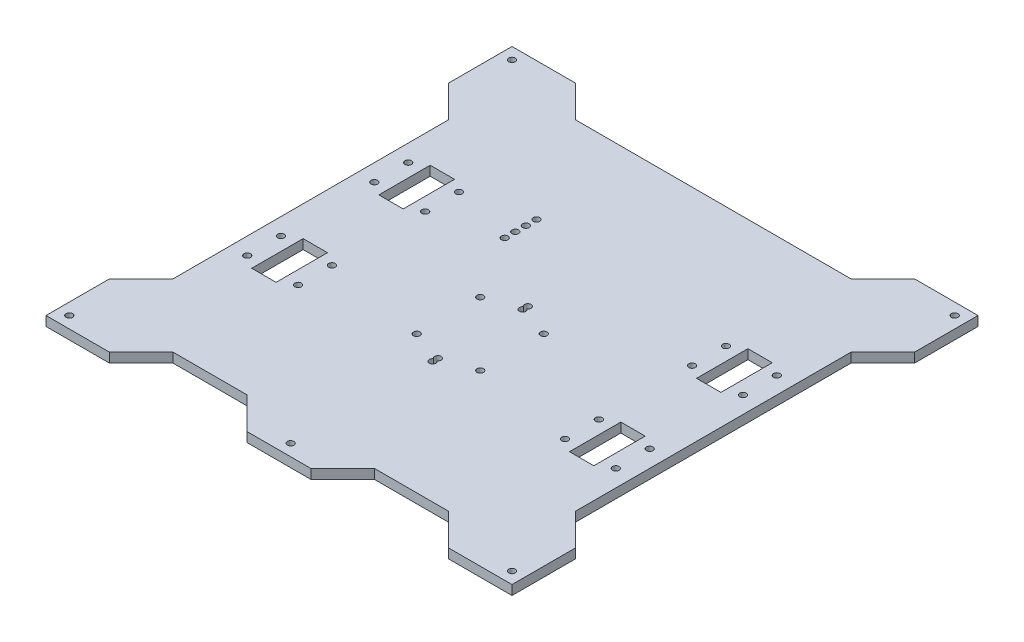
SolidWorks part; units mm, degrees
ref_plane "Front Plane" through (0, 0, 0) normal (0, 0, 1) x (1, 0, 0)
ref_plane "Top Plane" through (0, 0, 0) normal (0, 1, 0) x (1, 0, 0)
ref_plane "Right Plane" through (0, 0, 0) normal (1, 0, 0) x (0, 0, -1)
sketch "Sketch1" plane through (0, 0, 0) normal (0, 1, 0) x (1, 0, 0)
  line L1 (-110, 110) -> (110, 110)
  line L2 (-110, 110) -> (-110, -110)
  line L3 (-110, -110) -> (110, -110)
  line L4 (110, 110) -> (110, -110)
  line L5 (-110, 110) -> (110, -110) construction
  line L6 (-110, -110) -> (110, 110) construction
  point P0 (0, 0)
  dimension "D1" = 220
  dimension "D2" = 220
extrude "Square" add sketch "Sketch1" along normal blind 4.5
sketch "Sketch2" plane through (0, 4.5, 0) normal (0, 1, 0) x (1, 0, 0)
  line L0 (0, 110) -> (0, -110) construction
  line L1 (110, 110) -> (-110, 110) construction
  line L2 (-110, -110) -> (110, -110) construction
  line L3 (-110, 0) -> (110, 0) construction
  line L4 (-110, 110) -> (-110, -110) construction
  line L5 (110, -110) -> (110, 110) construction
  line L6 (75, 110) -> (75, -110) construction
  line L7 (75, 30) -> (0, 30) construction
  line L8 (75, -30) -> (0, -30) construction
  circle A0 centre (87, 38) radius 1.55
  circle A1 centre (87, 22) radius 1.55
  circle A2 centre (63, 22) radius 1.55
  circle A3 centre (63, 38) radius 1.55
  circle A4 centre (-63, 38) radius 1.55
  circle A5 centre (-63, 22) radius 1.55
  circle A6 centre (-87, 22) radius 1.55
  circle A7 centre (-87, 38) radius 1.55
  circle A8 centre (-87, 22) radius 1.55
  circle A9 centre (-87, 38) radius 1.55
  circle A10 centre (-63, 38) radius 1.55
  circle A11 centre (-63, 22) radius 1.55
  circle A12 centre (63, 22) radius 1.55
  circle A13 centre (63, 38) radius 1.55
  circle A14 centre (87, 38) radius 1.55
  circle A15 centre (87, 22) radius 1.55
  circle A16 centre (87, -22) radius 1.55
  circle A17 centre (87, -38) radius 1.55
  circle A18 centre (63, -38) radius 1.55
  circle A19 centre (63, -22) radius 1.55
  circle A20 centre (-63, -22) radius 1.55
  circle A21 centre (-63, -38) radius 1.55
  circle A22 centre (-87, -38) radius 1.55
  circle A23 centre (-87, -22) radius 1.55
  circle A24 centre (-87, -38) radius 1.55
  circle A25 centre (-87, -22) radius 1.55
  circle A26 centre (-63, -22) radius 1.55
  circle A27 centre (-63, -38) radius 1.55
  circle A28 centre (63, -38) radius 1.55
  circle A29 centre (63, -22) radius 1.55
  circle A30 centre (87, -22) radius 1.55
  circle A31 centre (87, -38) radius 1.55
  dimension "D6" = 3.1
  dimension "D7" = 3.1
  dimension "D1" = 75
  dimension "D2" = 30
  dimension "D3" = 16
  dimension "D5" = 12
extrude "LM8UU-Holders" cut sketch "Sketch2" against normal through all contours A7 | A6 | A5 | A4 | A20 | A21 | A22 | A23 | A19 | A18 | A17 | A16 | A1 | A0 | A3 | A2 region at (87, 4.5, -38) region at (87, 4.5, -22) region at (63, 4.5, -22) region at (63, 4.5, -38) region at (-63, 4.5, -38) region at (-63, 4.5, -22) region at (-87, 4.5, -22) region at (-87, 4.5, -38) region at (87, 4.5, 22) region at (87, 4.5, 38) region at (63, 4.5, 38) region at (63, 4.5, 22) region at (-63, 4.5, 22) region at (-63, 4.5, 38) region at (-87, 4.5, 38) region at (-87, 4.5, 22)
sketch "Sketch3" plane through (0, 4.5, 0) normal (0, 1, 0) x (1, 0, 0)
  line L0 (0, -110) -> (0, 110) construction
  line L1 (-110, -110) -> (110, -110) construction
  line L2 (110, 110) -> (-110, 110) construction
  line L3 (110, -15) -> (-110, -15) construction
  line L6 (15, -30) -> (-15, -30) construction
  line L7 (15, 0) -> (-15, 0) construction
  line L8 (110, -110) -> (110, 110) construction
  line L9 (-110, 110) -> (-110, -110) construction
  line L10 (110, 0) -> (-110, 0) construction
  circle A0 centre (-15, -30) radius 1.55
  circle A1 centre (15, -30) radius 1.55
  circle A2 centre (15, 0) radius 1.55
  circle A3 centre (-15, 0) radius 1.55
  point P16 (0, -30)
  dimension "D1" = 3.1
  dimension "D2" = 15
  dimension "D3" = 15
  dimension "D5" = 15
extrude "DefaultBelt" cut sketch "Sketch3" against normal through all
sketch "Sketch4" plane through (0, 4.5, 0) normal (0, 1, 0) x (1, 0, 0)
  line L0 (0, 110) -> (0, -110) construction
  line L1 (110, 110) -> (-110, 110) construction
  line L2 (-110, -110) -> (110, -110) construction
  line L3 (-15, -1.55) -> (-15, -28.45) construction
  line L4 (15, -28.45) -> (15, -1.55) construction
  line L5 (15, -15) -> (-15, -15) construction
  arc A0 (-0.9165, 6.25) -> (0.9165, 6.25) centre (0, 5) ccw
  arc A1 (0.9165, 6.25) -> (-0.9165, 6.25) centre (0, 7.5) ccw
  arc A2 (0.9165, -36.25) -> (-0.9165, -36.25) centre (0, -37.5) cw
  arc A3 (-0.9165, -36.25) -> (0.9165, -36.25) centre (0, -35) cw
  circle A4 centre (-15, 0) radius 1.55 construction
  circle A5 centre (-15, -30) radius 1.55 construction
  circle A6 centre (15, -30) radius 1.55 construction
  circle A7 centre (15, 0) radius 1.55 construction
  dimension "D1" = 3.1
  dimension "D2" = 3.1
  dimension "D3" = 20
  dimension "D4" = 22.5
extrude "BeltOptions" cut sketch "Sketch4" against normal through all
sketch "Sketch5" plane through (0, 4.5, 0) normal (0, 1, 0) x (1, 0, 0)
  line L0 (-110, 0) -> (110, 0) construction
  line L1 (-110, 110) -> (-110, -110) construction
  line L2 (110, -110) -> (110, 110) construction
  line L3 (0, 110) -> (0, -110) construction
  line L4 (110, 110) -> (-110, 110) construction
  line L5 (-110, 110) -> (-110, 80)
  line L6 (-110, 80) -> (-95, 65)
  line L7 (-95, 65) -> (-95, -65)
  line L8 (0, 0) -> (-110, 110) construction
  line L9 (-65, 95) -> (65, 95)
  line L10 (-80, 110) -> (-65, 95)
  line L11 (-110, 110) -> (-80, 110)
  line L12 (-95, 65) -> (-95, -65)
  line L13 (0, 0) -> (110, 110) construction
  line L14 (95, 65) -> (95, -65)
  line L15 (110, 110) -> (80, 110)
  line L16 (80, 110) -> (65, 95)
  line L17 (95, 65) -> (95, -65)
  line L18 (110, 80) -> (95, 65)
  line L19 (110, 110) -> (110, 80)
  line L20 (0, 0) -> (110, -110) construction
  line L21 (0, 0) -> (-110, -110) construction
  line L22 (110, -110) -> (110, -80)
  line L23 (110, -80) -> (95, -65)
  line L24 (80, -110) -> (65, -95)
  line L25 (110, -110) -> (80, -110)
  line L26 (-110, -110) -> (-80, -110)
  line L27 (-80, -110) -> (-65, -95)
  line L28 (-65, -95) -> (65, -95)
  line L29 (-110, -80) -> (-95, -65)
  line L30 (-110, -110) -> (-110, -80)
  point P24 (0, 95)
  point P32 (95, 0)
  point P35 (-95, 0)
  point P36 (0, -95)
  circle M16 centre (15, -30) radius 1.55
  circle M18 centre (63, 38) radius 1.55
  circle M20 centre (87, 22) radius 1.55
  circle M22 centre (87, -38) radius 1.55
  circle M23 centre (63, -38) radius 1.55
  circle M24 centre (63, -22) radius 1.55
  circle M25 centre (-87, -22) radius 1.55
  circle M26 centre (-87, -38) radius 1.55
  circle M27 centre (-63, -38) radius 1.55
  circle M28 centre (-63, -22) radius 1.55
  circle M29 centre (-63, 38) radius 1.55
  circle M30 centre (-63, 22) radius 1.55
  circle M31 centre (-87, 22) radius 1.55
  circle M32 centre (-87, 38) radius 1.55
  line M33 (110, -110) -> (110, 110)
  line M34 (110, 110) -> (-110, 110)
  line M35 (-110, 110) -> (-110, -110)
  line M36 (-110, -110) -> (110, -110)
  dimension "D1" = 15
  dimension "D2" = 30
  dimension "D3" = 45
  dimension "D4" = 45
extrude "Shaping" cut sketch "Sketch5" against normal blind 10 flip side to cut contours L29 L27 L28 L24 L23 L14 L18 L16 L9 L10 L6 L7 M35 M36 M33 M34 M16 M18 M20 M22 M24 M26 M28 M30 M32 M31 M29 M27 M25 M23 region at (0.0423, 4.5, -0.013)
sketch "Sketch6" plane through (0, 4.5, 0) normal (0, 1, 0) x (1, 0, 0)
  line L0 (-110, 110) -> (110, -110) construction
  line L1 (-110, -110) -> (110, 110) construction
  line L2 (110, 80) -> (110, 110) construction
  line L3 (0, 95) -> (0, -95) construction
  line L4 (-65, 95) -> (65, 95) construction
  line L5 (-65, -95) -> (65, -95) construction
  line L6 (-95, 0) -> (95, 0) construction
  line L7 (-95, 65) -> (-95, -65) construction
  line L8 (95, 65) -> (95, -65) construction
  circle A0 centre (-104.5, 104.5) radius 1.55
  circle A1 centre (104.5, 104.5) radius 1.55
  circle A2 centre (104.5, -104.5) radius 1.55
  circle A3 centre (-104.5, -104.5) radius 1.55
  dimension "D2" = 3.1
  dimension "D1" = 45
  dimension "D3" = 104.5
extrude "Cut-Extrude5" cut sketch "Sketch6" against normal through all
sketch "Sketch7" plane through (0, 4.5, 0) normal (0, 1, 0) x (1, 0, 0)
  line L0 (-87, 38) -> (-63, 22) construction
  line L1 (-63, 22) -> (-87, 22) construction
  line L2 (-87, 22) -> (-63, 38) construction
  line L3 (-63, 38) -> (-87, 38) construction
  line L4 (-95, 0) -> (95, 0) construction
  line L5 (-80.75, 42.125) -> (-69.25, 42.125)
  line L6 (-80.75, 42.125) -> (-80.75, 17.875)
  line L7 (-80.75, 17.875) -> (-69.25, 17.875)
  line L8 (-69.25, 42.125) -> (-69.25, 17.875)
  line L9 (-80.75, 42.125) -> (-69.25, 17.875) construction
  line L10 (-80.75, 17.875) -> (-69.25, 42.125) construction
  line L11 (-95, 65) -> (-95, -65) construction
  line L12 (95, 65) -> (95, -65) construction
  line L13 (0, -95) -> (0, 95) construction
  line L14 (-65, -95) -> (65, -95) construction
  line L15 (-65, 95) -> (65, 95) construction
  line L16 (-80.75, -17.875) -> (-69.25, -42.125) construction
  line L17 (-80.75, -42.125) -> (-69.25, -17.875) construction
  line L18 (-63, -38) -> (-87, -38) construction
  line L19 (-87, -22) -> (-63, -38) construction
  line L20 (-63, -22) -> (-87, -22) construction
  line L21 (-87, -38) -> (-63, -22) construction
  line L22 (-69.25, -42.125) -> (-69.25, -17.875)
  line L23 (-80.75, -17.875) -> (-69.25, -17.875)
  line L24 (-80.75, -42.125) -> (-80.75, -17.875)
  line L25 (-80.75, -42.125) -> (-69.25, -42.125)
  line L26 (-80.75, 17.875) -> (-69.25, 42.125) construction
  line L27 (80.75, 17.875) -> (69.25, 42.125) construction
  line L28 (87, -38) -> (63, -22) construction
  line L29 (63, -22) -> (87, -22) construction
  line L30 (87, -22) -> (63, -38) construction
  line L31 (63, -38) -> (87, -38) construction
  line L32 (80.75, -42.125) -> (69.25, -17.875) construction
  line L33 (80.75, -17.875) -> (69.25, -42.125) construction
  line L34 (80.75, 17.875) -> (69.25, 42.125) construction
  line L35 (80.75, 42.125) -> (69.25, 17.875) construction
  line L36 (63, 38) -> (87, 38) construction
  line L37 (87, 22) -> (63, 38) construction
  line L38 (63, 22) -> (87, 22) construction
  line L39 (87, 38) -> (63, 22) construction
  line L40 (80.75, -42.125) -> (69.25, -42.125)
  line L41 (80.75, -42.125) -> (80.75, -17.875)
  line L42 (80.75, -17.875) -> (69.25, -17.875)
  line L43 (69.25, -42.125) -> (69.25, -17.875)
  line L44 (69.25, 42.125) -> (69.25, 17.875)
  line L45 (80.75, 17.875) -> (69.25, 17.875)
  line L46 (80.75, 42.125) -> (80.75, 17.875)
  line L47 (80.75, 42.125) -> (69.25, 42.125)
  point P4 (-75, 30)
  point P33 (-75, -30)
  point P50 (75, -30)
  point P51 (75, 30)
  dimension "D1" = 11.5
  dimension "D2" = 24.25
extrude "Cut-Extrude6" cut sketch "Sketch7" against normal through all
sketch "Sketch8" plane through (0, 4.5, 0) normal (0, 1, 0) x (1, 0, 0)
  line L3 (-65, 95) -> (65, 95) construction
  line L4 (-33.45, 45) -> (-33.45, 30) construction
  circle A0 centre (-33.45, 45) radius 1.55
  circle A1 centre (-33.45, 40) radius 1.55
  circle A2 centre (-33.45, 35) radius 1.55
  circle A3 centre (-33.45, 30) radius 1.55
  dimension "D1" = 3.1
  dimension "D2" = 50
extrude "EndstopTrigger" cut sketch "Sketch8" against normal through all
pattern_linear "LPattern1" [suppressed] count 2 spacing 30 of bodies 108
sketch "Sketch9" plane through (0, 4.5, 0) normal (0, 1, 0) x (1, 0, 0)
  line L0 (-80, -110) -> (80, -110) construction
  line L1 (0, -110) -> (0, -95) construction
  line L2 (-65, -95) -> (65, -95) construction
  line L3 (15, -110) -> (-15, -110)
  line L4 (-15, -110) -> (-30, -95)
  line L5 (-30, -95) -> (30, -95)
  line L6 (-80, -110) -> (-65, -95) construction
  line L9 (15, -110) -> (30, -95)
  line L10 (-104.5, -104.5) -> (104.5, -104.5) construction
  circle A0 centre (0, -104.5) radius 1.55
  dimension "D2" = 15
  dimension "D3" = 3.1
  dimension "D1" = 90
extrude "Boss-Extrude1" add sketch "Sketch9" against normal through all
equation "\"X-ROD-SPACING\"=45"
equation "\"Y-ROD-SPACING\"=75"
equation "\"Z-ROD-SPACING\"=17.5"
equation "\"Y-BED-OFFSET\"=2"
equation "\"Y-BED-ROD-INSET\"=3.5"
equation "\"T-SLOT-NUT-FILLET-RADIUS\"=0.25"
equation "\"T-SLOT-SCREW-SHAFT-RADIUS\"=1.75"
equation "\"T-SLOT-SCREW-SHAFT-CUTOUT-LENGTH\"=10.5"
equation "\"T-SLOT-NUT-DEPTH\"=4.2"
equation "\"T-SLOT-NUT-WIDTH\"=3"
equation "\"T-SLOT-NUT-END-DISTANCE\"=8"
equation "\"ACRYLIC-THICKNESS\"=10"
equation "\"ACRYLIC-THICKNESS2\"=4.5"
equation "\"ACRYLIC-TAB-CUTOUT-SIZE\"=\"ACRYLIC-THICKNESS\"+\"ACRYLIC-TAB-TOLERANCE\"*2"
equation "\"ACRYLIC-TAB-WIDTH\"=\"ACRYLIC-THICKNESS\""
equation "\"ACRYLIC-M3-HOLE\"=3.1"
equation "\"SMOOTHROD-CAP-SCREW-DISTANCE\"=20"
equation "\"FRAME-WIDTH-INNER\"=370"
equation "\"NEMA17-HOLE-SPACING\"=31"
equation "\"NEMA17-CENTRAL-CUTOUT\"=22.5"
equation "\"Z-BRACKET-REACH\"=55"
equation "\"TOP-BRACKET-SPACING\"=40"
equation "\"SMOOTHROD-X-LENGTH\"=350"
equation "\"SMOOTHROD-Y-LENGTH\"=350"
equation "\"SMOOTHROD-Z-LENGTH\"=350"
equation "\"SMOOTHROD-TIGHTENING-HEADROOM\"=.25"
equation "\"LEADSCREW-Z-LENGTH\"=300"
equation "\"SCREW-LENGTH-FRAME\"=\"ACRYLIC-THICKNESS\" + 10"
equation "\"SCREW-HEAD-RADIUS\"=6"
equation "\"PRINTED-X-SMOOTHROD-DIAMETER\"=8.2"
equation "\"PRINTED-X-SMOOTHROD-CUTOUT\"=10"
equation "\"PRINTED-X-BASE-HEIGHT\"=10"
equation "\"PRINTED-LM8UU-CUTOUT-SIZE\"=15.25"
equation "\"PRINTED-LM8UU-CUTOUT-LENGTH\"=24.5"
equation "\"PRINTED-X-IDLER-HEIGHT\"=16"
equation "\"PSU-MOUNTING-WIDTH\"=95"
equation "\"PSU-MOUNTING-HEIGHT\"=177"
equation "\"Y-BELT-TO-ROD-DISTANCE\"=20"
equation "\"D6@Sketch2\"=\"ACRYLIC-M3-HOLE\""
equation "\"D7@Sketch2\"=\"ACRYLIC-M3-HOLE\""
equation "\"D1@Sketch2\"=\"Y-ROD-SPACING\""
equation "\"D1@Sketch3\"=\"ACRYLIC-M3-HOLE\""
equation "\"D2@Sketch6\"=\"ACRYLIC-M3-HOLE\""
equation "\"Y-BED-SCREW-SPACING\"=209"
equation "\"Y-BED-SCREW-CUTOUT-SLOT-HEIGHT\"=2"
equation "\"ACRYLIC-TAB-TOLERANCE\"=.1"
equation "\"Z-ROD-INSET\"=16"
equation "\"SCREW-LENGTH-MOTOR\"=\"ACRYLIC-THICKNESS\" + 5"
equation "\"SCREW-LENGTH-EXTRUDER\"=28"
equation "\"PRINTED-M3-HOLE\"=3.5"
equation "\"SPOOL-HOLDER-ROD-SPACING\"=150"
equation "\"ACRYLIC-X-CARRIAGE-WIDTH\"=55"
equation "\"ACRYLIC-X-CARRIAGE-HEIGHT\"=75"
equation "\"ACRYLIC-X-CARRIAGE-LM8UU-CUTOUT-WIDTH\"=24.25"
equation "\"ACRYLIC-X-CARRIAGE-LM8UU-CUTOUT-HEIGHT\"=11.5"
equation "\"ACRYLIC-X-CARRIAGE-SCREW-SPACING-X\"=15"
equation "\"ACRYLIC-X-CARRIAGE-SCREW-SPACING-Y\"=33"
equation "\"ACRYLIC-X-CARRIAGE-CENTER-TAB-SPACING\"=14"
equation "\"ACRYLIC-X-CARRIAGE-EXTRUDER-OFFSET\"=26"
equation "\"ACRYLIC-X-CARRIAGE-EXTRUDER-ANGLE\"=90"
equation "\"ACRYLIC-X-CARRIAGE-EXTRUDER-SHELF-DEPTH\"=\"ACRYLIC-X-CARRIAGE-EXTRUDER-OFFSET\" + 28"
equation "\"ACRYLIC-X-CARRIAGE-EXTRUDER-BRACE-SPACING\"=23"
equation "\"ACRYLIC-X-CARRIAGE-EXTRUDER-BRACE-TAB-OFFSET\"=20"
equation "\"ACRYLIC-X-CARRIAGE-EXTRUDER-BRACE-HEIGHT\"=35"
equation "\"ACRYLIC-X-CARRIAGE-EXTRUDER-BRACE-SCREW-SPACING\"=22"
equation "\"ACRYLIC-X-CARRIAGE-DUAL-WIDTH-MULTIPLIER\"=1.65"
equation "\"ACRYLIC-X-CARRIAGE-DUAL-HOTEND-SPACING\"=42"
equation "\"ACRYLIC-X-CARRIAGE-DUAL-WIDTH\"=95"
equation "\"ACRYLIC-X-CARRIAGE-DUAL-HOTEND-SEPARATION\"=35"
equation "\"ACRYLIC-X-CARRIAGE-DUAL-MOUNT-PLATE-DEPTH\"=75"
equation "\"ACRYLIC-X-CARRIAGE-DUAL-MOUNT-BRACE-WIDTH\"=33"
equation "\"ACRYLIC-X-CARRIAGE-DUAL-MOUNT-SCREW-WIDTH\"=40"
equation "\"BLOWER-FAN-WIDTH\"=15"
equation "\"D1@Sketch7\"=\"ACRYLIC-X-CARRIAGE-LM8UU-CUTOUT-HEIGHT\""
equation "\"D2@Sketch7\"=\"ACRYLIC-X-CARRIAGE-LM8UU-CUTOUT-WIDTH\""
equation "\"D1@Sketch8\"=\"ACRYLIC-M3-HOLE\""
equation "\"D2@Sketch4\"=\"ACRYLIC-M3-HOLE\""
equation "\"D1@Sketch4\"=\"ACRYLIC-M3-HOLE\""
equation "\"D3@Sketch4\"=20"
equation "\"D3@Sketch9\"=\"ACRYLIC-M3-HOLE\""
